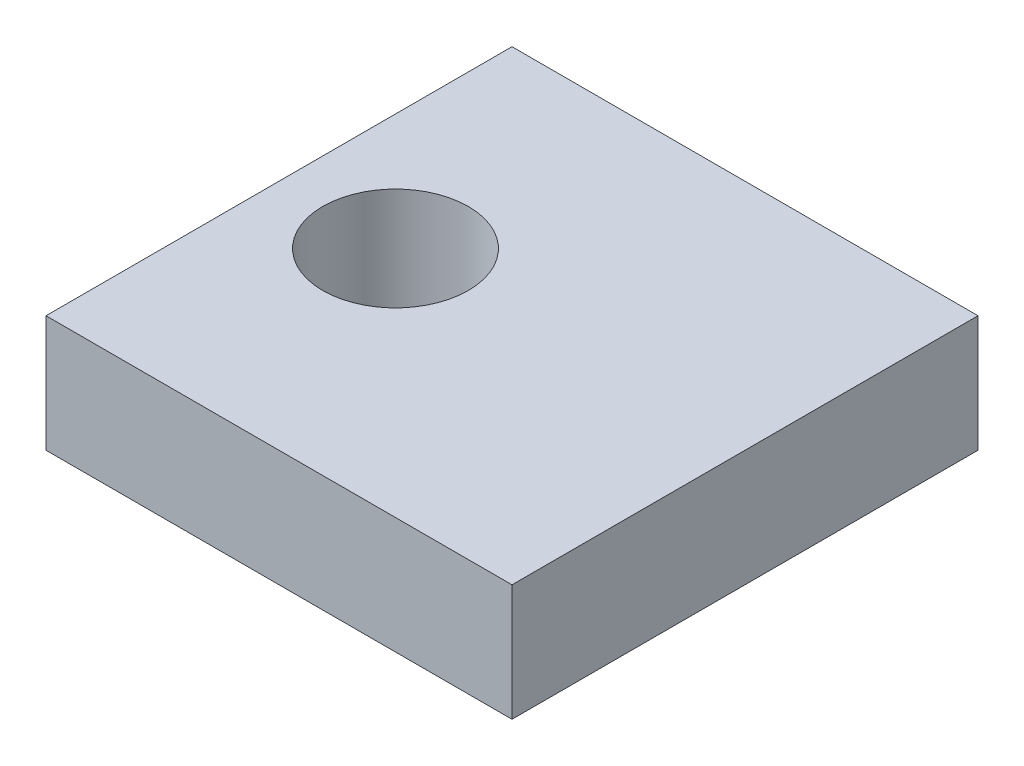
SolidWorks part; units mm, degrees
ref_plane "Front" through (0, 0, 0) normal (0, 0, 1) x (1, 0, 0)
ref_plane "Top" through (0, 0, 0) normal (0, 1, 0) x (1, 0, 0)
ref_plane "Right" through (0, 0, 0) normal (1, 0, 0) x (0, 0, -1)
sketch "Sketch1" plane through (0, 0, 0) normal (0, 1, 0) x (1, 0, 0)
  line L1 (-50.8, -50.8) -> (50.8, -50.8)
  line L2 (-50.8, -50.8) -> (-50.8, 50.8)
  line L3 (-50.8, 50.8) -> (50.8, 50.8)
  line L4 (50.8, -50.8) -> (50.8, 50.8)
  line L5 (-50.8, -50.8) -> (50.8, 50.8) construction
  line L6 (-50.8, 50.8) -> (50.8, -50.8) construction
  point P0 (0, 0)
  dimension "D1" = 101.6
  dimension "D2" = 101.6
extrude "Boss-Extrude1" add sketch "Sketch1" along normal mid plane 25.4
sketch "Sketch2" plane through (0, 12.7, 0) normal (0, 1, 0) x (1, 0, 0)
  line L0 (-50, 0) -> (50, 0) construction
  line L1 (-50.8, 50.8) -> (-50.8, -50.8) construction
  circle A0 centre (-25.4, 0) radius 15.875
  dimension "D2" = 31.75
  dimension "D1" = 25.4
extrude "Cut-Extrude1" cut sketch "Sketch2" against normal through all both and the other way through all
